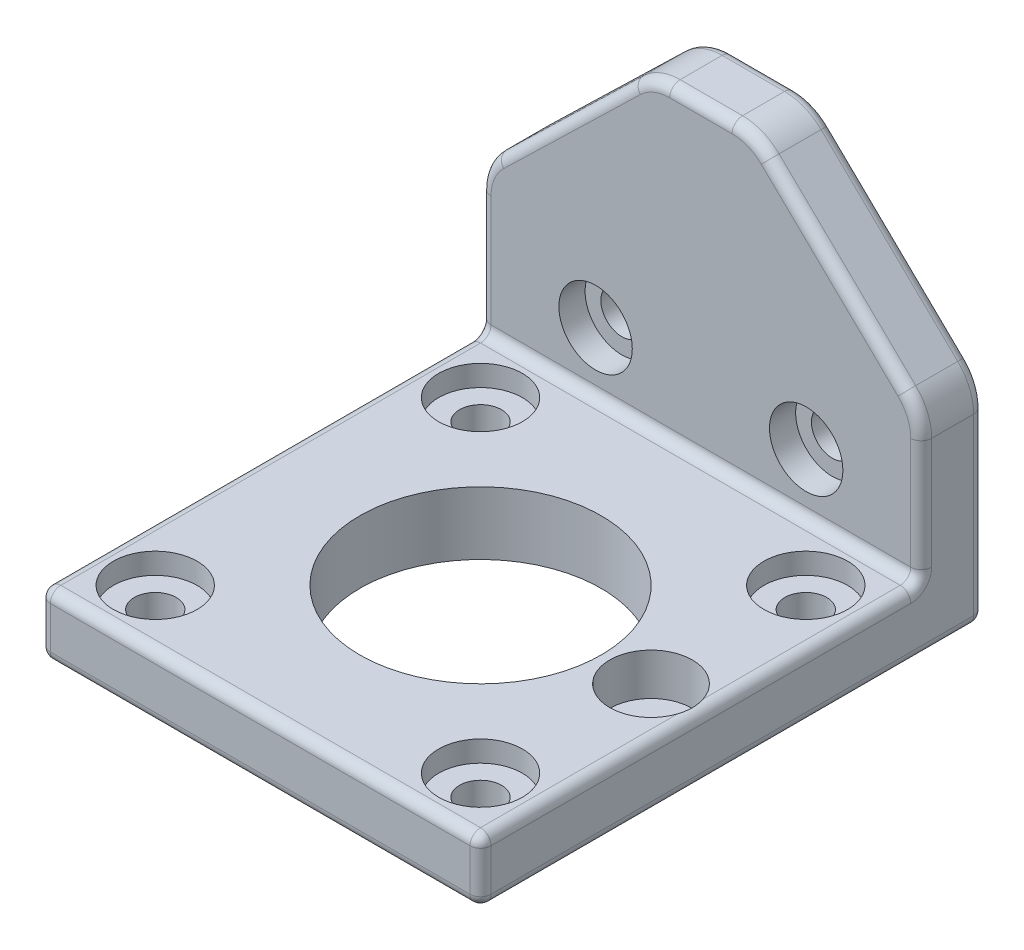
SolidWorks part; units mm, degrees
ref_plane "Front Plane" through (0, 0, 0) normal (0, 0, 1) x (1, 0, 0)
ref_plane "Top Plane" through (0, 0, 0) normal (0, 1, 0) x (1, 0, 0)
ref_plane "Right Plane" through (0, 0, 0) normal (1, 0, 0) x (0, 0, -1)
sketch "Sketch1" plane through (0, 0, 0) normal (0, 1, 0) x (1, 0, 0)
  line L1 (-21, 21) -> (21, 21)
  line L2 (-21, 21) -> (-21, -21)
  line L3 (-21, -21) -> (21, -21)
  line L4 (21, 21) -> (21, -21)
  line L5 (-21, 21) -> (21, -21) construction
  line L6 (-21, -21) -> (21, 21) construction
  point P0 (0, 0)
  dimension "D1" = 42
  dimension "D2" = 42
extrude "Boss-Extrude1" add sketch "Sketch1" along normal blind 6
sketch "Sketch3" plane through (0, 6, 0) normal (0, 1, 0) x (1, 0, 0)
  line L0 (0, -15.5) -> (0, 15.5) construction
  line L1 (-15.5, 0) -> (15.5, 0) construction
  line L2 (-15.5, 15.5) -> (15.5, 15.5) construction
  line L3 (15.5, 15.5) -> (15.5, -15.5) construction
  line L4 (15.5, -15.5) -> (-15.5, -15.5) construction
  line L5 (-15.5, -15.5) -> (-15.5, 15.5) construction
  circle A0 centre (-15.5, 15.5) radius 3.9905
  circle A1 centre (15.5, 15.5) radius 3.9905
  circle A2 centre (-15.5, -15.5) radius 3.9905
  circle A3 centre (15.5, -15.5) radius 3.9905
  point P12 (0, 0)
  point P16 (0, 0)
  point P17 (0, 15.5)
  point P20 (15.5, 0)
  dimension "D1" = 7.981
  dimension "D2" = 31
  dimension "D3" = 31
extrude "Cut-Extrude1" cut sketch "Sketch3" against normal blind 2
sketch "Sketch4" plane through (0, 6, 0) normal (0, 1, 0) x (1, 0, 0)
  circle A0 centre (0, 0) radius 11.5
  circle A1 centre (15.5, 15.5) radius 2
  circle A2 centre (-15.5, 15.5) radius 2
  circle A3 centre (-15.5, -15.5) radius 2
  circle A4 centre (15.5, -15.5) radius 2
  dimension "D1" = 4
  dimension "D2" = 23
extrude "Cut-Extrude2" cut sketch "Sketch4" against normal through all
sketch "Sketch5" plane through (0, 0, -21) normal (0, 0, -1) x (-1, 0, 0)
  line L0 (0, 9.875) -> (0, 19.75) construction
  line L2 (-21, 19.75) -> (-21, 0)
  line L3 (-21, 0) -> (21, 0)
  line L4 (21, 19.75) -> (21, 0)
  line L5 (-21, 19.75) -> (21, 0) construction
  line L6 (-21, 0) -> (21, 19.75) construction
  line L7 (-5, 35.25) -> (5, 35.25)
  line L13 (5, 35.25) -> (21, 19.75)
  line L14 (-5, 35.25) -> (-21, 19.75)
  point P0 (0, 9.875)
  point P6 (0, 27.5)
  dimension "D1" = 35.25
  dimension "D2" = 19.75
  dimension "D3" = 16
  dimension "D4" = 16
  dimension "D5" = 15.5
extrude "Boss-Extrude2" add sketch "Sketch5" along normal blind 6
sketch "Sketch6" plane through (0, 0, -21) normal (0, 0, 1) x (1, 0, 0)
  line L0 (-10.035, 11.75) -> (10.035, 11.75) construction
  line L1 (0, 11.75) -> (0, 0) construction
  circle A0 centre (-10.035, 11.75) radius 3.5
  circle A1 centre (10.035, 11.75) radius 3.5
  dimension "D1" = 7
  dimension "D2" = 7
  dimension "D3" = 11.75
  dimension "D4" = 20.07
extrude "Cut-Extrude3" cut sketch "Sketch6" against normal blind 2.5
sketch "Sketch7" plane through (0, 0, -21) normal (0, 0, 1) x (1, 0, 0)
  circle A0 centre (-10.035, 11.75) radius 2
  circle A1 centre (10.035, 11.75) radius 2
  dimension "D1" = 4
extrude "Cut-Extrude4" cut sketch "Sketch7" against normal through all
fillet "Fillet1" radius 5 4 edges at (21, 19.75, -24) (5, 35.25, -24) (-5, 35.25, -24) (-21, 19.75, -24)
sketch "Sketch8" plane through (0, 6, 0) normal (0, 1, 0) x (1, 0, 0)
  line L0 (0, 0) -> (16.25, 0) construction
  circle A0 centre (16.25, 0) radius 3.9365
  dimension "D1" = 7.873
  dimension "D2" = 16.25
extrude "Cut-Extrude5" cut sketch "Sketch8" against normal blind 4
fillet "Fillet2" radius 1 28 edges at (21, 6, 0) (21, 11.8161, -21) (20.6041, 19.5823, -21) (12.9666, 27.5323, -21) (4.852, 34.8844, -21) (0, 35.25, -21) (-4.852, 34.8844, -21) (-12.9666, 27.5323, -21) (-20.6041, 19.5823, -21) (-21, 11.8161, -21) (-21, 8.8161, -27) (-20.6041, 19.5823, -27) (-12.9666, 27.5323, -27) (-4.852, 34.8844, -27) (0, 35.25, -27) (4.852, 34.8844, -27) (12.9666, 27.5323, -27) (20.6041, 19.5823, -27) (21, 8.8161, -27) (0, 0, -27) (21, 0, -3) (0, 0, 21) (-21, 0, -3) (0, 6, 21) (-21, 6, 0) (0, 6, -21) (21, 3, 21) (-21, 3, 21)
